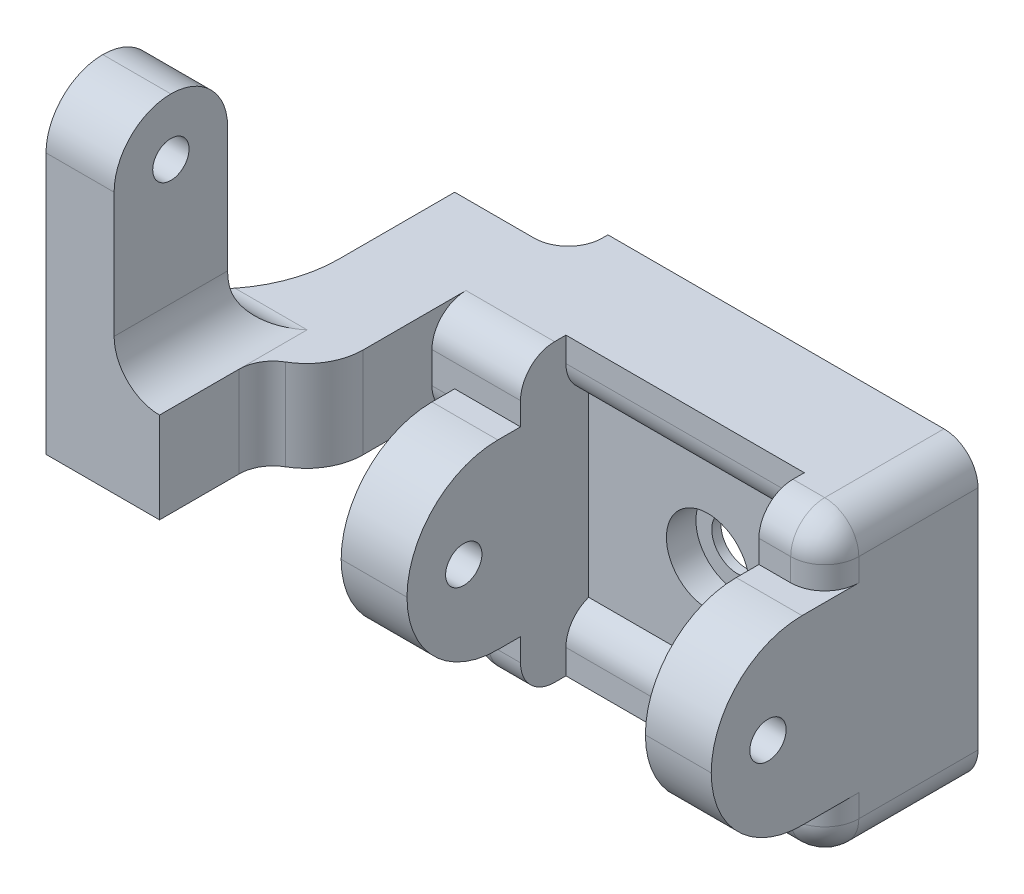
SolidWorks part; units mm, degrees
ref_plane "Front" through (0, 0, 0) normal (0, 0, 1) x (1, 0, 0)
ref_plane "Top" through (0, 0, 0) normal (0, 1, 0) x (1, 0, 0)
ref_plane "Right" through (0, 0, 0) normal (1, 0, 0) x (0, 0, -1)
sketch "Sketch1" plane through (0, 0, 0) normal (0, 0, 1) x (1, 0, 0)
  line L1 (0, 0) -> (-32.6, 0)
  line L2 (0, 0) -> (0, 26)
  line L3 (0, 26) -> (-32.6, 26)
  line L4 (-32.6, 0) -> (-32.6, 26)
  dimension "D1" = 32.6
  dimension "D2" = 26
extrude "Boss-Extrude1" add sketch "Sketch1" along normal blind 4
sketch "Sketch2" plane through (0, 0, 4) normal (0, 0, 1) x (1, 0, 0)
  line L0 (0, 26) -> (-32.6, 26) construction
  line L1 (0, 0) -> (0, 26) construction
  circle A0 centre (-16.3, 13) radius 3.65
  dimension "D1" = 7.3
  dimension "D2" = 13
  dimension "D3" = 16.3
extrude "Cut-Extrude1" cut sketch "Sketch2" against normal blind 2.6
sketch "Sketch3" plane through (0, 0, 1.4) normal (0, 0, 1) x (1, 0, 0)
  circle A0 centre (-16.3, 13) radius 2.25
  dimension "D1" = 4.5
extrude "Cut-Extrude2" cut sketch "Sketch3" against normal through all
sketch "Sketch4" plane through (0, 0, 4) normal (0, 0, 1) x (1, 0, 0)
  line L0 (-32.6, 0) -> (0, 0) construction
  line L1 (0, 26) -> (-5.8, 26)
  line L2 (0, 26) -> (0, 0)
  line L3 (0, 0) -> (-5.8, 0)
  line L4 (-5.8, 26) -> (-5.8, 0)
  line L6 (-32.6, 26) -> (-26.8, 26)
  line L7 (-32.6, 26) -> (-32.6, 0)
  line L8 (-32.6, 0) -> (-26.8, 0)
  line L9 (-26.8, 26) -> (-26.8, 0)
  dimension "D1" = 5.8
  dimension "D2" = 5.8
extrude "Boss-Extrude2" add sketch "Sketch4" along normal blind 16
sketch "Sketch5" plane through (0, 0, 0) normal (1, 0, 0) x (0, 0, -1)
  line L0 (-20, 0) -> (-20, 26) construction
  line L1 (-20, 0) -> (0, 0) construction
  circle A0 centre (-15, 13) radius 1.6
  dimension "D1" = 3.2
  dimension "D2" = 5
  dimension "D3" = 13
extrude "Cut-Extrude3" cut sketch "Sketch5" against normal through all
sketch "Sketch6" plane through (0, 0, 4) normal (0, 0, 1) x (1, 0, 0)
  line L1 (-26.8, 26) -> (-5.8, 26)
  line L2 (-26.8, 26) -> (-26.8, 21)
  line L3 (-26.8, 21) -> (-5.8, 21)
  line L4 (-5.8, 26) -> (-5.8, 21)
  line L5 (-26.8, 0) -> (-5.8, 0)
  line L6 (-26.8, 0) -> (-26.8, 5)
  line L7 (-26.8, 5) -> (-5.8, 5)
  line L8 (-5.8, 0) -> (-5.8, 5)
  dimension "D1" = 5
  dimension "D2" = 5
extrude "Boss-Extrude3" add sketch "Sketch6" along normal blind 2
sketch "Sketch7" plane through (-32.6, 0, 0) normal (-1, 0, 0) x (0, 0, 1)
  line L1 (20, 26) -> (10, 26)
  line L2 (20, 26) -> (20, 21)
  line L3 (20, 21) -> (10, 21)
  line L4 (10, 26) -> (10, 21)
  line L5 (20, 0) -> (10, 0)
  line L6 (20, 0) -> (20, 5)
  line L7 (20, 5) -> (10, 5)
  line L8 (10, 0) -> (10, 5)
  dimension "D1" = 10
  dimension "D2" = 10
  dimension "D3" = 5
  dimension "D4" = 5
extrude "Cut-Extrude4" cut sketch "Sketch7" against normal through all
fillet "Fillet1" radius 8 4 edges at (-2.9, 5, 20) (-2.9, 21, 20) (-29.7, 5, 20) (-29.7, 21, 20)
sketch "Sketch12" plane through (-32.6, 0, 0) normal (-1, 0, 0) x (0, 0, 1)
  line L0 (0, 26) -> (0, 0) construction
  line L1 (10, 26) -> (0, 26)
  line L2 (10, 26) -> (10, 18)
  line L3 (10, 18) -> (0, 18)
  line L4 (0, 26) -> (0, 18)
  dimension "D1" = 8
extrude "Boss-Extrude8" add sketch "Sketch12" along normal blind 10
sketch "Sketch13" plane through (0, 0, 10) normal (0, 0, 1) x (1, 0, 0)
  line L0 (-26.8, 26) -> (-42.6, 26) construction
  line L1 (-42.6, 18) -> (-34.6, 18)
  line L2 (-42.6, 18) -> (-42.6, 26)
  line L3 (-42.6, 26) -> (-34.6, 26)
  line L4 (-34.6, 18) -> (-34.6, 26)
  dimension "D1" = 8
extrude "Boss-Extrude9" add sketch "Sketch13" along normal blind 10
fillet "Fillet2" radius 3 4 edges at (-30.7, 26, 10) (-2.9, 26, 10) (-2.9, 0, 10) (-29.7, 0, 10)
sketch "Sketch14" plane through (0, 0, 20) normal (0, 0, 1) x (1, 0, 0)
  line L0 (-42.6, 18) -> (-34.6, 18) construction
  line L1 (-38.6, 18) -> (-48.6, 18)
  line L2 (-38.6, 18) -> (-38.6, 26)
  line L3 (-38.6, 26) -> (-48.6, 26)
  line L4 (-48.6, 18) -> (-48.6, 26)
  dimension "D1" = 8
  dimension "D2" = 10
extrude "Boss-Extrude10" add sketch "Sketch14" along normal blind 10
sketch "Sketch15" plane through (0, 26, 0) normal (0, 1, 0) x (1, 0, 0)
  line L1 (-48.6, -30) -> (-42.6, -30)
  line L2 (-48.6, -30) -> (-48.6, -20)
  line L3 (-48.6, -20) -> (-42.6, -20)
  line L4 (-42.6, -30) -> (-42.6, -20)
  dimension "D1" = 10
  dimension "D2" = 6
extrude "Boss-Extrude11" add sketch "Sketch15" along normal blind 20
fillet "Fillet10" radius 11 1 edges at (-42.6, 22, 20)
fillet "Fillet11" radius 3 1 edges at (-38.6, 22, 20)
fillet "Fillet12" radius 5 1 edges at (-34.6, 22, 20)
fillet "Fillet14" radius 4 1 edges at (-42.6, 26, 25)
fillet "Fillet15" radius 3 1 edges at (-43.6, 26, 20)
sketch "Sketch16" plane through (0, 0, 0) normal (0, 0, -1) x (-1, 0, 0)
  line L0 (42.6, 18) -> (32.6, 18)
  line L1 (32.6, 18) -> (32.6, 9)
  line L2 (32.6, 18) -> (32.6, 0) construction
  line L3 (32.6, 9) -> (42.6, 18)
  dimension "D1" = 9
extrude "Boss-Extrude12" add sketch "Sketch16" against normal blind 9
fillet "Fillet17" radius 3 1 edges at (-32.6, 9, 4.5)
fillet "Fillet18" radius 3 1 edges at (-33.6, 18, 10)
sketch "Sketch17" plane through (-48.6, 0, 0) normal (-1, 0, 0) x (0, 0, 1)
  line L0 (30, 46) -> (30, 18) construction
  line L1 (20, 46) -> (30, 46) construction
  circle A0 centre (25, 41) radius 1.6
  dimension "D1" = 3.2
  dimension "D2" = 5
  dimension "D3" = 5
extrude "Cut-Extrude5" cut sketch "Sketch17" against normal through all
fillet "Fillet19" radius 5 2 edges at (-45.6, 46, 20) (-45.6, 46, 30)
fillet "Fillet21" radius 3 2 edges at (-16.3, 21, 6) (-16.3, 5, 6)
sketch "Sketch18" plane through (0, 0, 0) normal (0, 0, -1) x (-1, 0, 0)
  line L0 (0, 0) -> (0, 26) construction
  line L1 (32.6, 0) -> (0, 0)
  line L2 (32.6, 0) -> (32.6, 26)
  line L3 (32.6, 26) -> (0, 26)
  line L4 (0, 0) -> (0, 26)
extrude "Boss-Extrude13" add sketch "Sketch18" along normal blind 3.5
sketch "Sketch19" plane through (0, 0, -3.5) normal (0, 0, -1) x (-1, 0, 0)
  circle A0 centre (16.3, 13) radius 9.15
  dimension "D1" = 18.3
extrude "Cut-Extrude6" cut sketch "Sketch19" against normal blind 4.1
fillet "Fillet22" radius 3 9 edges at (0, 22, 10) (0, 25.1213, 9.1213) (0, 4, 10) (0, 0.8787, 9.1213) (-32.6, 4, 10) (-32.6, 0.8787, 9.1213) (0, 26, 1.75) (0, 0, 1.75) (-32.6, 0, 1.75)
fillet "Fillet23" radius 3 1 edges at (-32.6, 16.832, 0)
sketch "Sketch20" plane through (0, 0, 0) normal (0, -1, 0) x (-1, 0, 0)
  line L0 (3, 3.5) -> (29.6, 3.5) construction
  line L1 (3, 3.5) -> (3, -7) construction
  circle A0 centre (16.3, 0.5) radius 1
  dimension "D3" = 2
  dimension "D1" = 3
  dimension "D2" = 13.3
extrude "Cut-Extrude7" cut sketch "Sketch20" against normal blind 4
